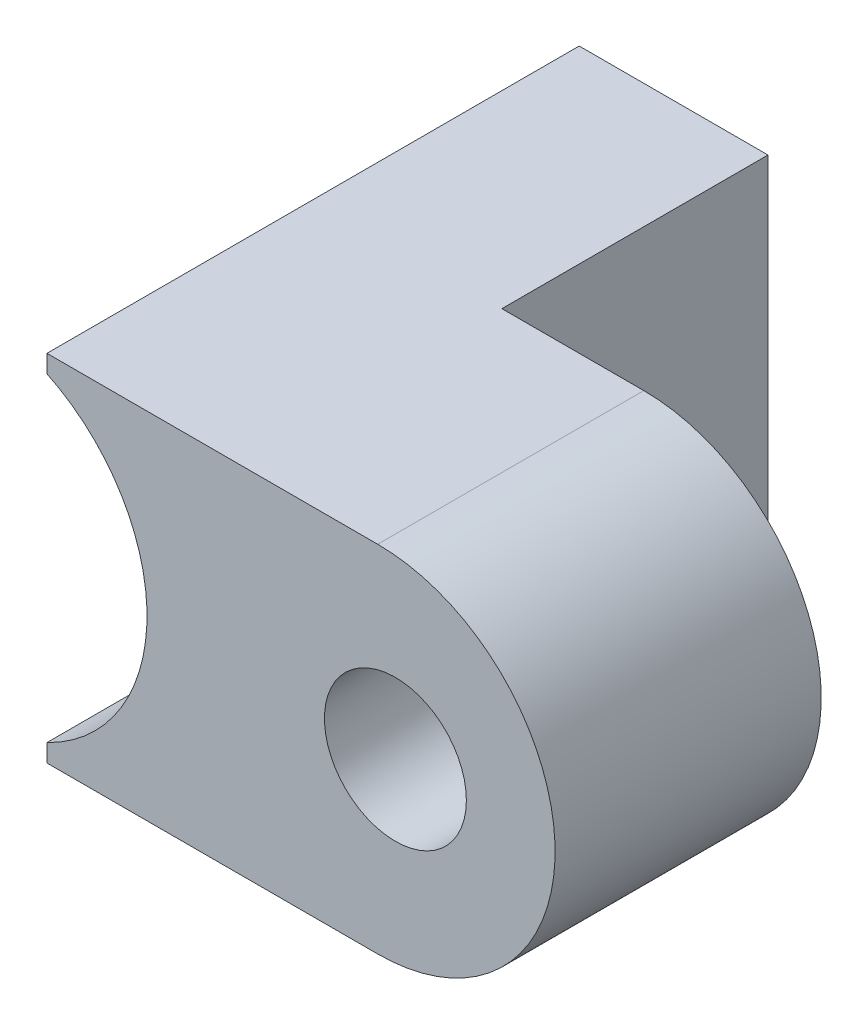
SolidWorks part; units mm, degrees
material "AISI Type A2 Tool Steel Custom"
ref_plane "Front Plane" through (0, 0, 0) normal (0, 0, 1) x (1, 0, 0)
ref_plane "Top Plane" through (0, 0, 0) normal (0, 1, 0) x (1, 0, 0)
ref_plane "Right Plane" through (0, 0, 0) normal (1, 0, 0) x (0, 0, -1)
sketch "Sketch1" plane through (0, 0, 0) normal (0, 0, 1) x (1, 0, 0)
  line L1 (5.5358, 0) -> (29.21, 0)
  line L3 (5.5358, 25.4) -> (29.21, 25.4)
  line L5 (5.5358, 25.4) -> (5.5358, 24.13)
  line L8 (5.5358, 1.27) -> (5.5358, 0)
  arc A1 (5.5358, 1.27) -> (5.5358, 24.13) centre (0, 12.7) ccw
  arc A4 (29.21, 0) -> (29.21, 25.4) centre (29.21, 12.7) ccw
  point P3 (41.91, 12.7)
  dimension "D2" = 25.4
  dimension "D5" = 5.5358
  dimension "D3" = 41.91
  dimension "D1" = 12.7
  dimension "D4" = 1.27
extrude "Boss-Extrude1" add sketch "Sketch1" along normal blind 38.1
sketch "Sketch2" plane through (0, 0, 0) normal (0, 0, -1) x (-1, 0, 0)
  line L0 (-19.05, 0) -> (-19.05, 25.4)
  line L1 (-5.5358, 0) -> (-29.21, 0) construction
  line L2 (-29.21, 25.4) -> (-5.5358, 25.4) construction
  line L3 (-5.5358, 0) -> (-29.21, 0) construction
  line L4 (-29.21, 25.4) -> (-5.5358, 25.4) construction
  line L5 (-19.05, 0) -> (-29.21, 0)
  line L10 (-29.21, 25.4) -> (-19.05, 25.4)
  arc A1 (-29.21, 25.4) -> (-29.21, 0) centre (-29.21, 12.7) ccw construction
  arc A3 (-29.21, 25.4) -> (-29.21, 0) centre (-29.21, 12.7) ccw
  point P9 (-29.4442, 0.0022)
  dimension "D1" = 19.05
extrude "Cut-Extrude1" cut sketch "Sketch2" against normal blind 19.05
sketch "Sketch3" plane through (0, 0, 38.1) normal (0, 0, 1) x (1, 0, 0)
  line L0 (5.5358, 0) -> (29.21, 0) construction
  arc A0 (29.21, 0) -> (29.21, 25.4) centre (29.21, 12.7) ccw construction
  point P0 (30.48, 12.7)
  point P13 (41.91, 12.7)
  dimension "D1" = 12.7
  dimension "D2" = 11.43
hole_wizard "3/8 (0.375) Diameter Hole1" positions "Sketch3" profile "Sketch4" hole size "3/8" standard "ANSI Inch" end condition through all
sketch "Sketch4" plane through (30.48, 12.7, 38.1) normal (1, 0, 0) x (0, -1, 0)
  line L0 (0, 0) -> (0, 38.1)
  line L1 (0, 38.1) -> (5.08, 38.1)
  line L2 (5.08, 38.1) -> (5.08, 0)
  line L5 (5.08, 0) -> (0, 0)
  line L11 (0, -6.35) -> (0, 107.95) construction
  dimension "Thru Hole Dia." = 10.16
  dimension "Thru Hole Depth" = 38.1
chamfer "Chamfer1" distance 1.27 angle 45 1 edges at (19.05, 0, 9.525)
